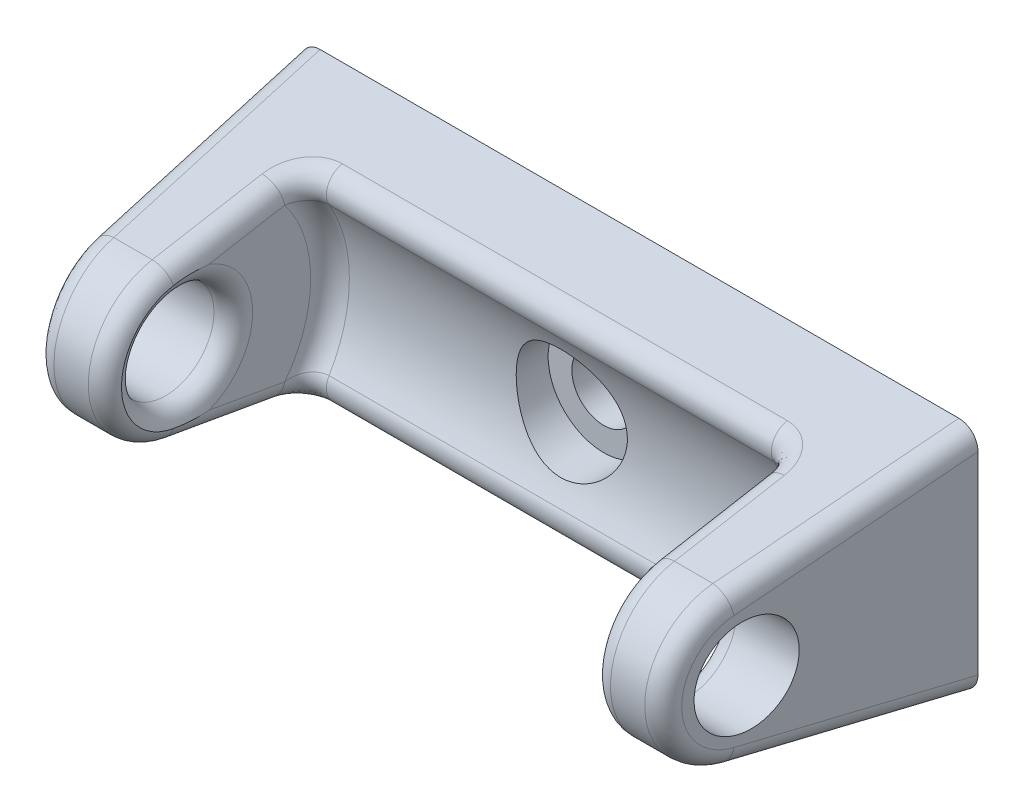
SolidWorks part; units mm, degrees
ref_plane "前基準面" through (0, 0, 0) normal (0, 0, 1) x (1, 0, 0)
ref_plane "上基準面" through (0, 0, 0) normal (0, 1, 0) x (1, 0, 0)
ref_plane "右基準面" through (0, 0, 0) normal (1, 0, 0) x (0, 0, -1)
sketch "草圖2" plane through (0, 0, 0) normal (1, 0, 0) x (0, 0, -1)
  line L5 (0, 12) -> (0, -12)
  line L11 (-23.3883, 7.8786) -> (0, 12)
  line L12 (-23.3883, -7.8786) -> (0, -12)
  circle A3 centre (-22, 0) radius 5
  arc A4 (-23.3883, 7.8786) -> (-23.3883, -7.8786) centre (-22, 0) ccw
  point P2 (0, 0)
  dimension "D3" = 8
  dimension "D4" = 10
  dimension "D5" = 22
  dimension "D1" = 24
extrude "填料-伸長1" add sketch "草圖2" against normal mid plane 70
ref_plane "平面1" [suppressed] through (34.7341, 0, 3.0388) normal (0.9962, 0, 0.0872) x (0, 1, 0)
sketch "草圖10" plane through (0, 0, 0) normal (0, 1, 0) x (1, 0, 0)
  line L0 (-35, 0) -> (35, 0)
  line L1 (35, 0) -> (32.3753, -30)
  line L2 (-35, -30) -> (35, -30) construction
  line L3 (32.3753, -30) -> (-32.3753, -30)
  line L4 (-32.3753, -30) -> (-35, 0)
  line L5 (-35, 0) -> (-35, -23.3883) construction
  line L6 (35, 0) -> (35, -23.3883) construction
  dimension "D1" = 5
  dimension "D2" = 5
extrude "除料-伸長2" cut sketch "草圖10" against normal through all both and the other way through all flip side to cut
sketch "草圖11" plane through (0, 0, 0) normal (1, 0, 0) x (0, 0, -1)
  line L0 (-23.3883, 7.8786) -> (0, 12) construction
  line L1 (0, -12) -> (-23.3883, -7.8786) construction
  line L2 (-23.3883, -7.8786) -> (-10.8923, -10.0806)
  line L3 (-23.3883, 7.8786) -> (-10.8923, 10.0806)
  circle A0 centre (-22, 0) radius 5
  arc A1 (-23.3883, -7.8786) -> (-23.3883, 7.8786) centre (-22, 0) cw
  arc A2 (-23.3883, 7.8786) -> (-23.3883, -7.8786) centre (-22, 0) ccw construction
  arc A3 (-10.8923, 10.0806) -> (-10.8923, -10.0806) centre (-22, 0) cw
  dimension "D1" = 15
  dimension "D2" = 10
extrude "除料-伸長3" cut sketch "草圖11" against normal mid plane 50
sketch "草圖12" plane through (0, 0, 0) normal (1, 0, 0) x (0, 0, -1)
  line L0 (-6.55, 0) -> (2.0925, 0) construction
  line L2 (-8.1458, 5.75) -> (-3.7, 5.75)
  line L3 (-3.7, 5.75) -> (-3.7, 3.3)
  line L4 (-3.7, 3.3) -> (0, 3.3)
  line L5 (0, -12) -> (0, 12) construction
  line L6 (0, 3.3) -> (0, 0)
  line L7 (0, 0) -> (-7, 0)
  arc A0 (-10.8923, -10.0806) -> (-10.8923, 10.0806) centre (-22, 0) ccw construction
  arc A2 (-8.1458, 5.75) -> (-7, 0) centre (-22, 0) cw
  point P16 (0, 0)
  dimension "D1" = 3.3
  dimension "D2" = 11.5
  dimension "D3" = 6.6
revolve "除料-旋轉1" cut sketch "草圖12" angle 360 about L0
fillet "圓角2" radius 2 12 edges at (25, -8.9796, 17.1403) (25, 0, 30) (-25, -8.9796, 17.1403) (-25, 0, 30) (25, 8.9796, 17.1403) (-25, 8.9796, 17.1403) (0, -10.0806, 10.8923) (-25, 0, 7) (0, 10.0806, 10.8923) (25, 0, 7) (-25, 0, 17) (25, 0, 17)
fillet "圓角5" radius 2 6 edges at (33.9769, -9.9393, 11.6942) (32.3753, 0, 30) (-33.9769, -9.9393, 11.6942) (-32.3753, 0, 30) (33.9769, 9.9393, 11.6942) (-33.9769, 9.9393, 11.6942)
